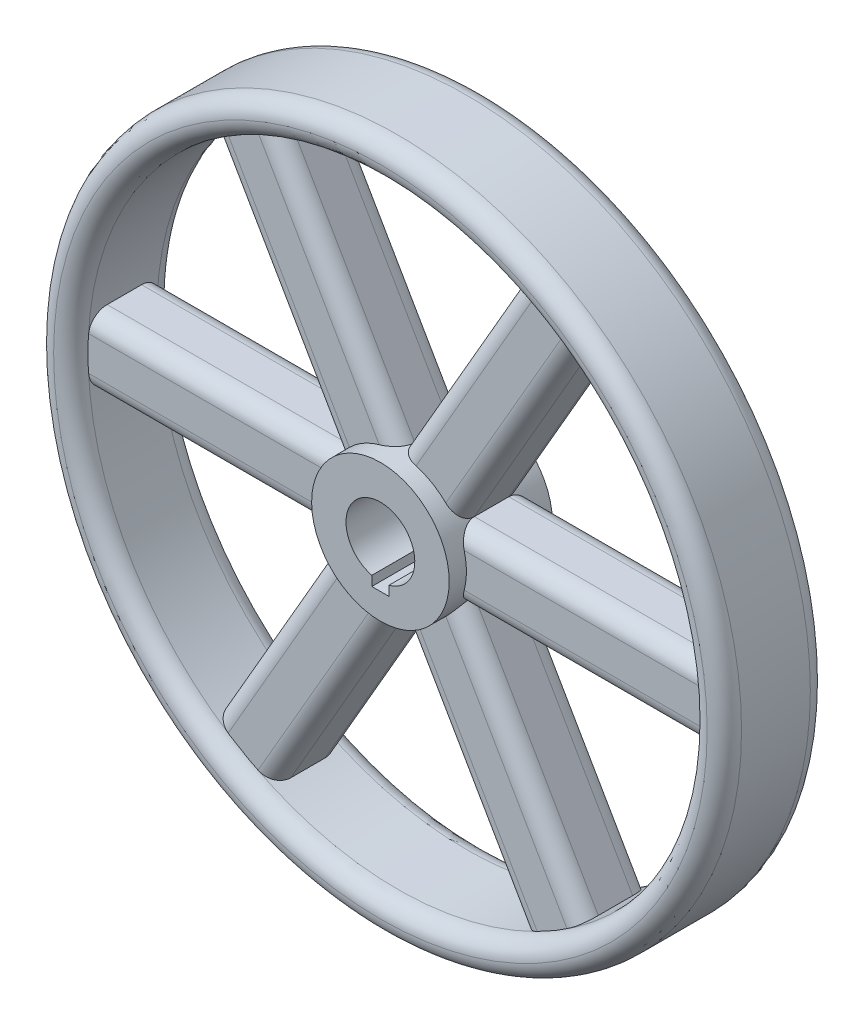
SolidWorks part; units mm, degrees
ref_plane "Front Plane" through (0, 0, 0) normal (0, 0, 1) x (1, 0, 0)
ref_plane "Top Plane" through (0, 0, 0) normal (0, 1, 0) x (1, 0, 0)
ref_plane "Right Plane" through (0, 0, 0) normal (1, 0, 0) x (0, 0, -1)
sketch "Sketch1" plane through (0, 0, 0) normal (0, 0, 1) x (1, 0, 0)
  circle A0 centre (0, 0) radius 100
  circle A1 centre (0, 0) radius 1
  circle A2 centre (0, 0) radius 90
  dimension "D1" = 200
  dimension "D2" = 180
extrude "Boss-Extrude1" add sketch "Sketch1" along normal blind 30 contours A0 A2
fillet "Fillet2" radius 5 4 edges at (90, 0, 30) (100, 0, 30) (90, 0, 0) (100, 0, 0)
sketch "Sketch2" plane through (0, 0, 0) normal (0, 0, 1) x (1, 0, 0)
  circle A0 centre (0, 0) radius 10
  circle A1 centre (0, 0) radius 20
  dimension "D1" = 20
  dimension "D2" = 40
extrude "Boss-Extrude2" add sketch "Sketch2" along normal blind 30 separate body
sketch "Sketch5" plane through (0, 0, 30) normal (0, 0, 1) x (1, 0, 0)
  line L1 (-2.5, -7.5) -> (2.5, -7.5)
  line L2 (-2.5, -7.5) -> (-2.5, -12.5)
  line L3 (-2.5, -12.5) -> (2.5, -12.5)
  line L4 (2.5, -7.5) -> (2.5, -12.5)
  line L5 (-2.5, -7.5) -> (2.5, -12.5) construction
  line L6 (-2.5, -12.5) -> (2.5, -7.5) construction
  circle A0 centre (0, 0) radius 10 construction
  point P0 (0, -10)
  dimension "D1" = 5
  dimension "D2" = 5
extrude "Cut-Extrude1" cut sketch "Sketch5" against normal blind 185
sketch3d "3DSketch1" plane through (0, 0, 0) normal (0, 0, 1) x (1, 0, 0)
  dimension "D1" = 20
sketch "Sketch4" plane through (20, 0, 0) normal (1, 0, 0) x (0, 0, -1)
  line L1 (-25, 10) -> (-5, 10)
  line L2 (-25, 10) -> (-25, -10)
  line L3 (-25, -10) -> (-5, -10)
  line L4 (-5, 10) -> (-5, -10)
  line L7 (-30, 20) -> (-30, -20) construction
  line L9 (0, 20) -> (-30, 20) construction
  dimension "D1" = 20
  dimension "D2" = 20
  dimension "D3" = 5
  dimension "D4" = 10
extrude "Boss-Extrude4" add sketch "Sketch4" along normal blind 75 and the other way blind 5 contours L1 L4 L3 L2
pattern_circular "CirPattern3" count 6 every 60 about axis through (0, 0, 0) along (0, 0, 1) of "Boss-Extrude4"
fillet "Fillet7" radius 5 4 edges at (19.4199, -53.6362, 5) (36.7404, -43.6362, 5) (19.4199, -53.6362, 25) (36.7404, -43.6362, 25)
fillet "Fillet8" radius 5 4 edges at (56.1603, -10, 25) (56.1603, 10, 25) (56.1603, 10, 5) (56.1603, -10, 5)
fillet "Fillet9" radius 5 6 edges at (17.3205, 10, 22.5) (17.3205, 10, 7.5) (36.7404, 43.6362, 5) (36.7404, 43.6362, 25) (19.4199, 53.6362, 5) (19.4199, 53.6362, 25)
fillet "Fillet10" radius 5 4 edges at (-19.4199, 53.6362, 5) (-19.4199, 53.6362, 25) (-36.7404, 43.6362, 5) (-36.7404, 43.6362, 25)
fillet "Fillet11" radius 5 6 edges at (-17.3205, 10, 7.5) (-17.3205, 10, 22.5) (-56.1603, 10, 25) (-56.1603, -10, 5) (-56.1603, 10, 5) (-56.1603, -10, 25)
fillet "Fillet12" radius 5 8 edges at (0, -20, 7.5) (0, -20, 22.5) (-17.3205, -10, 22.5) (-17.3205, -10, 7.5) (-36.7404, -43.6362, 25) (-19.4199, -53.6362, 5) (-36.7404, -43.6362, 5) (-19.4199, -53.6362, 25)
